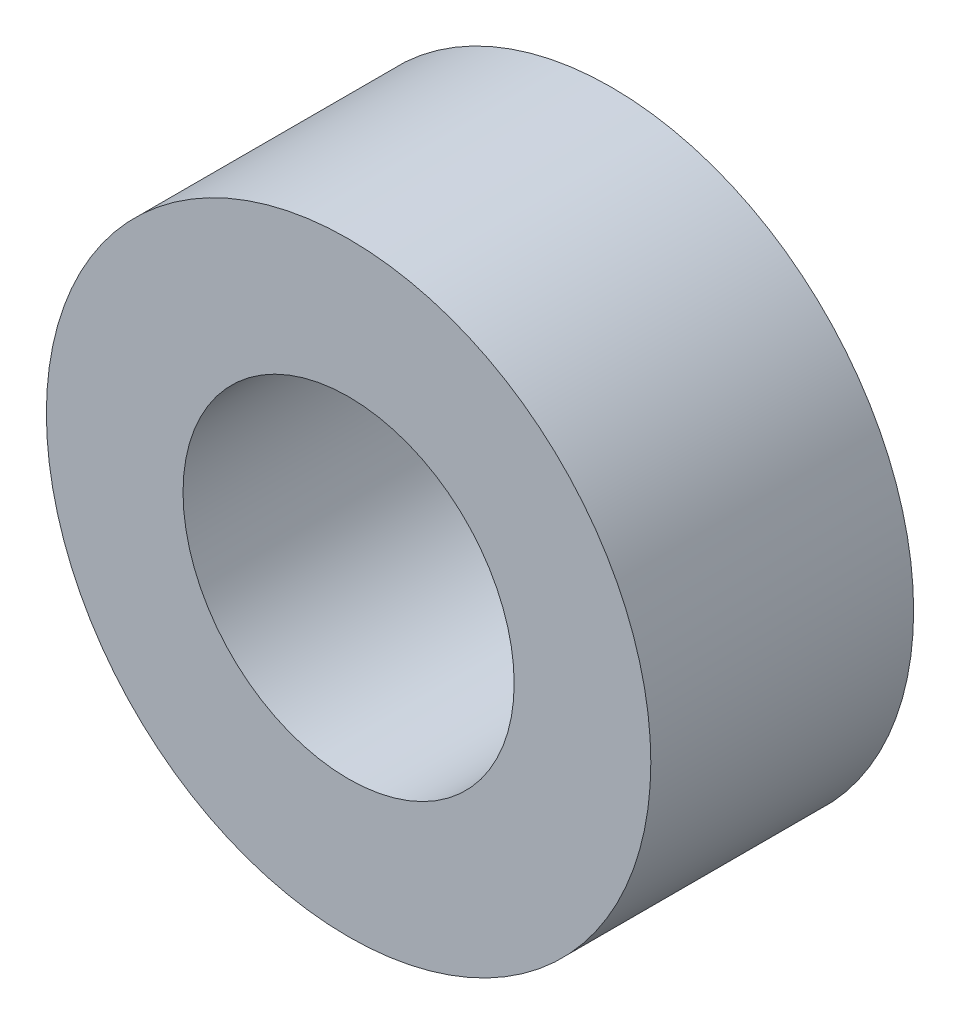
SolidWorks part; units mm, degrees
ref_plane "Front Plane" through (0, 0, 0) normal (0, 0, 1) x (1, 0, 0)
ref_plane "Top Plane" through (0, 0, 0) normal (0, 1, 0) x (1, 0, 0)
ref_plane "Right Plane" through (0, 0, 0) normal (1, 0, 0) x (0, 0, -1)
sketch "Sketch1" plane through (0, 0, 0) normal (0, 0, 1) x (1, 0, 0)
  circle A0 centre (0, 0) radius 2.875
  circle A1 centre (0, 0) radius 1.575
  dimension "D1" = 5.75
  dimension "D2" = 3.15
extrude "Boss-Extrude1" add sketch "Sketch1" along normal blind 2.5
